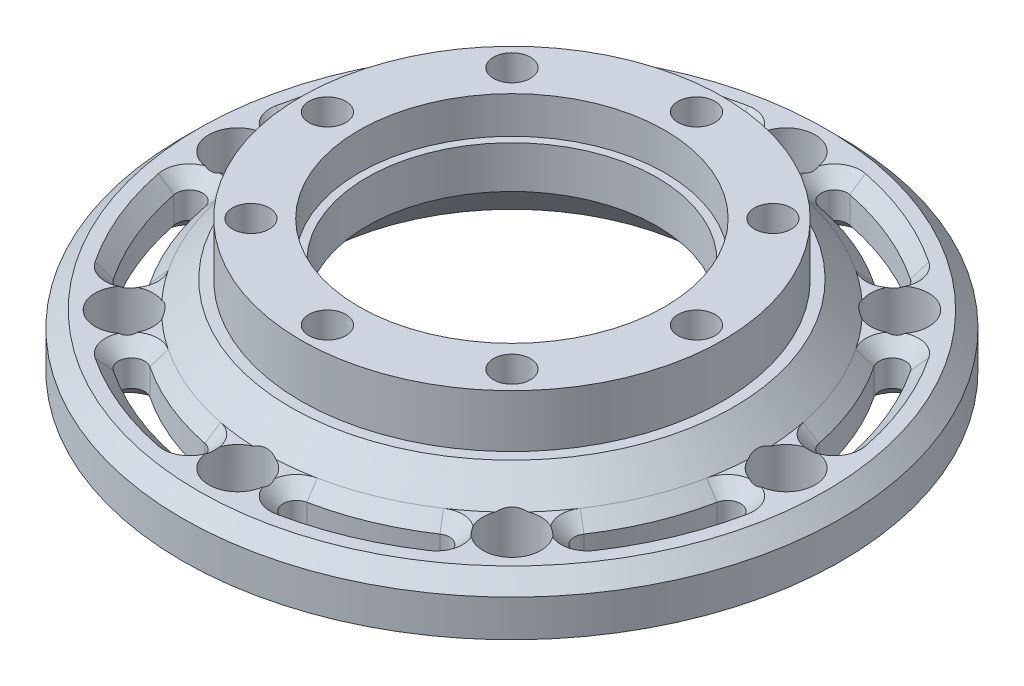
SolidWorks part; units mm, degrees
ref_plane "Front Plane" through (0, 0, 0) normal (0, 0, 1) x (1, 0, 0)
ref_plane "Top Plane" through (0, 0, 0) normal (0, 1, 0) x (1, 0, 0)
ref_plane "Right Plane" through (0, 0, 0) normal (1, 0, 0) x (0, 0, -1)
sketch "Sketch1" plane through (0, 0, 0) normal (0, 1, 0) x (1, 0, 0)
  circle A0 centre (0, 0) radius 52
  circle A1 centre (-52, 0) radius 5.5
  circle A2 centre (-36.7696, 36.7696) radius 5.5
  circle A3 centre (0, 52) radius 5.5
  circle A4 centre (36.7696, 36.7696) radius 5.5
  circle A5 centre (52, 0) radius 5.5
  circle A6 centre (36.7696, -36.7696) radius 5.5
  circle A7 centre (0, -52) radius 5.5
  circle A8 centre (-36.7696, -36.7696) radius 5.5
  circle A9 centre (0, 0) radius 41.5
  circle A10 centre (0, 0) radius 62.5
  point P21 (0, 0)
  dimension "D1" = 8
extrude "Boss-Extrude1" add sketch "Sketch1" along normal blind 10 contours A8 A0 A7 A6 A5 A4 A3 A2 A1 A9 | A10 A8 A0 A1 A2 A3 A4 A5 A6 A7 region at (45.0374, 0, 0) region at (-60.7322, 0, 0)
sketch "Sketch2" plane through (0, 10, 0) normal (0, 1, 0) x (1, 0, 0)
  line L0 (-40, 0) -> (-30, 0)
  circle A0 centre (0, 0) radius 40
  circle A1 centre (0, 0) radius 30
  circle A2 centre (-35, 0) radius 3.5
  circle A3 centre (-24.7487, 24.7487) radius 3.5
  circle A4 centre (0, 35) radius 3.5
  circle A5 centre (24.7487, 24.7487) radius 3.5
  circle A6 centre (35, 0) radius 3.5
  circle A7 centre (24.7487, -24.7487) radius 3.5
  circle A8 centre (0, -35) radius 3.5
  circle A9 centre (-24.7487, -24.7487) radius 3.5
  point P25 (0, 0)
  circle M10 centre (0, 0) radius 41.5
  dimension "D1" = 8
extrude "Boss-Extrude2" add sketch "Sketch2" along normal mid plane 20 contours A0 M10 | A2 A1 A0 A9 A8 A7 A6 A5 A4 A3 region at (0, 10, -38.8686) region at (-40.3262, 10, 0)
sketch "Sketch3" plane through (0, 20, 0) normal (0, 1, 0) x (1, 0, 0)
  circle A0 centre (-35, 0) radius 3.5
  circle A1 centre (-24.7487, 24.7487) radius 3.5
  circle A2 centre (0, 35) radius 3.5
  circle A3 centre (24.7487, 24.7487) radius 3.5
  circle A4 centre (35, 0) radius 3.5
  circle A5 centre (24.7487, -24.7487) radius 3.5
  circle A6 centre (0, -35) radius 3.5
  circle A7 centre (-24.7487, -24.7487) radius 3.5
  point P19 (0, 0)
  dimension "D1" = 8
extrude "Boss-Extrude3" add sketch "Sketch3" against normal blind 10 from offset 10 offset against normal yes
sketch "Sketch4" plane through (0, 20, 0) normal (0, 1, 0) x (1, 0, 0)
  circle A0 centre (0, 0) radius 40
  circle A1 centre (0, 0) radius 41.5
extrude "Cut-Extrude1" cut sketch "Sketch4" against normal blind 10
sketch "Sketch5" plane through (0, 10, 0) normal (0, 1, 0) x (1, 0, 0)
  circle A0 centre (0, 0) radius 42
  circle A1 centre (0, 0) radius 40
extrude "Boss-Extrude4" add sketch "Sketch5" along normal blind 5
sketch "Sketch6" plane through (0, 20, 0) normal (0, 1, 0) x (1, 0, 0)
  circle A0 centre (0, 0) radius 40
  circle A1 centre (0, 0) radius 30
  circle A2 centre (-35, 0) radius 3.5
  circle A3 centre (-24.7487, 24.7487) radius 3.5
  circle A4 centre (0, 35) radius 3.5
  circle A5 centre (24.7487, 24.7487) radius 3.5
  circle A6 centre (35, 0) radius 3.5
  circle A7 centre (24.7487, -24.7487) radius 3.5
  circle A8 centre (0, -35) radius 3.5
  circle A9 centre (-24.7487, -24.7487) radius 3.5
  point P23 (0, 0)
  dimension "D1" = 8
extrude "Boss-Extrude5" add sketch "Sketch6" along normal blind 5
chamfer "Chamfer1" distance 3 angle 45 1 edges at (0, 10, 62.5)
sketch "Sketch9" plane through (0, 10, 0) normal (0, 1, 0) x (1, 0, 0)
  arc A1 (-51.0008, 10.1447) -> (-43.2364, 28.8897) centre (0, 0) cw construction
  arc A2 (-45.3151, 30.2786) -> (-53.4528, 10.6324) centre (0, 0) ccw
  arc A3 (-41.1577, 27.5007) -> (-48.5489, 9.657) centre (0, 0) ccw
  arc A4 (-41.1577, 27.5007) -> (-45.3151, 30.2786) centre (-43.2364, 28.8897) ccw
  arc A5 (-53.4528, 10.6324) -> (-48.5489, 9.657) centre (-51.0008, 10.1447) ccw
  arc A6 (-28.8897, 43.2364) -> (-10.1447, 51.0008) centre (0, 0) cw construction
  arc A7 (-10.6324, 53.4528) -> (-30.2786, 45.3151) centre (0, 0) ccw
  arc A8 (-9.657, 48.5489) -> (-27.5007, 41.1577) centre (0, 0) ccw
  arc A9 (-9.657, 48.5489) -> (-10.6324, 53.4528) centre (-10.1447, 51.0008) ccw
  arc A10 (-30.2786, 45.3151) -> (-27.5007, 41.1577) centre (-28.8897, 43.2364) ccw
  arc A11 (10.1447, 51.0008) -> (28.8897, 43.2364) centre (0, 0) cw construction
  arc A12 (30.2786, 45.3151) -> (10.6324, 53.4528) centre (0, 0) ccw
  arc A13 (27.5007, 41.1577) -> (9.657, 48.5489) centre (0, 0) ccw
  arc A14 (27.5007, 41.1577) -> (30.2786, 45.3151) centre (28.8897, 43.2364) ccw
  arc A15 (10.6324, 53.4528) -> (9.657, 48.5489) centre (10.1447, 51.0008) ccw
  arc A16 (43.2364, 28.8897) -> (51.0008, 10.1447) centre (0, 0) cw construction
  arc A17 (53.4528, 10.6324) -> (45.3151, 30.2786) centre (0, 0) ccw
  arc A18 (48.5489, 9.657) -> (41.1577, 27.5007) centre (0, 0) ccw
  arc A19 (48.5489, 9.657) -> (53.4528, 10.6324) centre (51.0008, 10.1447) ccw
  arc A20 (45.3151, 30.2786) -> (41.1577, 27.5007) centre (43.2364, 28.8897) ccw
  arc A21 (51.0008, -10.1447) -> (43.2364, -28.8897) centre (0, 0) cw construction
  arc A22 (45.3151, -30.2786) -> (53.4528, -10.6324) centre (0, 0) ccw
  arc A23 (41.1577, -27.5007) -> (48.5489, -9.657) centre (0, 0) ccw
  arc A24 (41.1577, -27.5007) -> (45.3151, -30.2786) centre (43.2364, -28.8897) ccw
  arc A25 (53.4528, -10.6324) -> (48.5489, -9.657) centre (51.0008, -10.1447) ccw
  arc A26 (28.8897, -43.2364) -> (10.1447, -51.0008) centre (0, 0) cw construction
  arc A27 (10.6324, -53.4528) -> (30.2786, -45.3151) centre (0, 0) ccw
  arc A28 (9.657, -48.5489) -> (27.5007, -41.1577) centre (0, 0) ccw
  arc A29 (9.657, -48.5489) -> (10.6324, -53.4528) centre (10.1447, -51.0008) ccw
  arc A30 (30.2786, -45.3151) -> (27.5007, -41.1577) centre (28.8897, -43.2364) ccw
  arc A31 (-10.1447, -51.0008) -> (-28.8897, -43.2364) centre (0, 0) cw construction
  arc A32 (-30.2786, -45.3151) -> (-10.6324, -53.4528) centre (0, 0) ccw
  arc A33 (-27.5007, -41.1577) -> (-9.657, -48.5489) centre (0, 0) ccw
  arc A34 (-27.5007, -41.1577) -> (-30.2786, -45.3151) centre (-28.8897, -43.2364) ccw
  arc A35 (-10.6324, -53.4528) -> (-9.657, -48.5489) centre (-10.1447, -51.0008) ccw
  arc A36 (-43.2364, -28.8897) -> (-51.0008, -10.1447) centre (0, 0) cw construction
  arc A37 (-53.4528, -10.6324) -> (-45.3151, -30.2786) centre (0, 0) ccw
  arc A38 (-48.5489, -9.657) -> (-41.1577, -27.5007) centre (0, 0) ccw
  arc A39 (-48.5489, -9.657) -> (-53.4528, -10.6324) centre (-51.0008, -10.1447) ccw
  arc A40 (-45.3151, -30.2786) -> (-41.1577, -27.5007) centre (-43.2364, -28.8897) ccw
  point P9 (-48.0417, 19.8995)
  point P14 (-19.8995, 48.0417)
  point P21 (19.8995, 48.0417)
  point P28 (48.0417, 19.8995)
  point P35 (48.0417, -19.8995)
  point P42 (19.8995, -48.0417)
  point P49 (-19.8995, -48.0417)
  point P56 (-48.0417, -19.8995)
  point P61 (0, 0)
  dimension "D1" = 8
extrude "Cut-Extrude4" cut sketch "Sketch9" against normal blind 13
chamfer "Chamfer3" distance 2.5 angle 45 32 edges at (-41.8475, 10, 30.9683) (-45.732, 10, 18.9428) (-50.3514, 10, 20.8562) (-51.4886, 10, 7.6927) (-51.4886, 10, -7.6927) (-45.732, 10, -18.9428) (-50.3514, 10, -20.8562) (-41.8475, 10, -30.9683) (-30.9683, 10, -41.8475) (-18.9428, 10, -45.732) (-20.8562, 10, -50.3514) (-7.6927, 10, -51.4886) (7.6927, 10, -51.4886) (18.9428, 10, -45.732) (20.8562, 10, -50.3514) (30.9683, 10, -41.8475) (41.8475, 10, -30.9683) (45.732, 10, -18.9428) (50.3514, 10, -20.8562) (51.4886, 10, -7.6927) (51.4886, 10, 7.6927) (50.3514, 10, 20.8562) (41.8475, 10, 30.9683) (45.732, 10, 18.9428) (20.8562, 10, 50.3514) (30.9683, 10, 41.8475) (7.6927, 10, 51.4886) (18.9428, 10, 45.732) (-7.6927, 10, 51.4886) (-20.8562, 10, 50.3514) (-30.9683, 10, 41.8475) (-18.9428, 10, 45.732)
chamfer "Chamfer4" distance 2.5 angle 45 32 edges at (-51.4886, 0, -7.6927) (-45.732, 0, -18.9428) (-50.3514, 0, -20.8562) (-41.8475, 0, -30.9683) (-7.6927, 0, -51.4886) (-20.8562, 0, -50.3514) (-18.9428, 0, -45.732) (-30.9683, 0, -41.8475) (30.9683, 0, -41.8475) (20.8562, 0, -50.3514) (18.9428, 0, -45.732) (7.6927, 0, -51.4886) (51.4886, 0, -7.6927) (50.3514, 0, -20.8562) (45.732, 0, -18.9428) (41.8475, 0, -30.9683) (51.4886, 0, 7.6927) (45.732, 0, 18.9428) (50.3514, 0, 20.8562) (41.8475, 0, 30.9683) (30.9683, 0, 41.8475) (18.9428, 0, 45.732) (20.8562, 0, 50.3514) (7.6927, 0, 51.4886) (-7.6927, 0, 51.4886) (-18.9428, 0, 45.732) (-20.8562, 0, 50.3514) (-30.9683, 0, 41.8475) (-41.8475, 0, 30.9683) (-45.732, 0, 18.9428) (-50.3514, 0, 20.8562) (-51.4886, 0, 7.6927)
sketch "Sketch11" plane through (0, 25, 0) normal (0, 1, 0) x (1, 0, 0)
  circle A0 centre (0, 0) radius 30
  circle A1 centre (0, 0) radius 29
extrude "Boss-Extrude6" add sketch "Sketch11" against normal blind 25
sketch "Sketch13" plane through (0, 25, 0) normal (0, 1, 0) x (1, 0, 0)
  circle A0 centre (0, 0) radius 29
  circle A1 centre (0, 0) radius 27.5
extrude "Boss-Extrude7" add sketch "Sketch13" against normal blind 18 from offset 7 offset against normal yes
chamfer "Chamfer5" distance 10 angle 45 1 edges at (0, 0, 27.5)
chamfer "Chamfer6" distance 5 angle 45 1 edges at (0, 10, 42)
sketch "Sketch14" plane through (0, 25, 0) normal (0, 1, 0) x (1, 0, 0)
  circle A0 centre (-35, 0) radius 3.5
  circle A1 centre (-24.7487, 24.7487) radius 3.5
  circle A2 centre (0, 35) radius 3.5
  circle A3 centre (24.7487, 24.7487) radius 3.5
  circle A4 centre (35, 0) radius 3.5
  circle A5 centre (24.7487, -24.7487) radius 3.5
  circle A6 centre (0, -35) radius 3.5
  circle A7 centre (-24.7487, -24.7487) radius 3.5
  point P19 (0, 0)
  dimension "D1" = 8
extrude "Boss-Extrude8" add sketch "Sketch14" against normal blind 5 from offset 10 offset against normal yes
